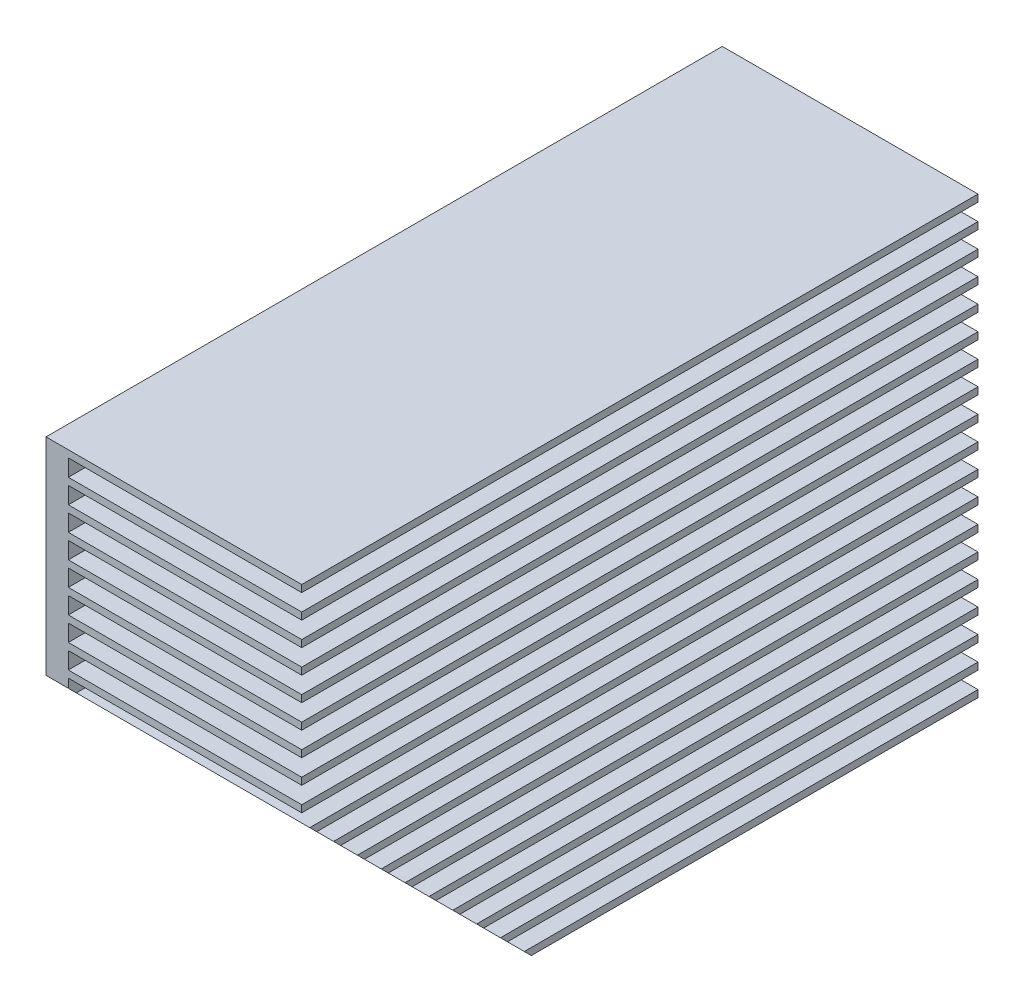
SolidWorks part; units mm, degrees
ref_plane "Front Plane" through (0, 0, 0) normal (0, 0, 1) x (1, 0, 0)
ref_plane "Top Plane" through (0, 0, 0) normal (0, 1, 0) x (1, 0, 0)
ref_plane "Right Plane" through (0, 0, 0) normal (1, 0, 0) x (0, 0, -1)
ref_axis "Axis1" through (0, -55, 0) along (0, 1, 0)
sketch "Sketch1" plane through (0, 0, 0) normal (1, 0, 0) x (0, 0, -1)
  line L1 (48.0658, 31) -> (-48.0658, 31)
  line L2 (48.0658, 31) -> (48.0658, -31)
  line L3 (48.0658, -31) -> (-48.0658, -31)
  line L4 (-48.0658, 31) -> (-48.0658, -31)
  line L5 (48.0658, 31) -> (-48.0658, -31) construction
  line L6 (48.0658, -31) -> (-48.0658, 31) construction
  point P0 (0, 0)
  dimension "D1" = 96.1315
  dimension "D2" = 62
extrude "Boss-Extrude1" add sketch "Sketch1" along normal blind 3.175
sketch "Sketch2" plane through (3.175, 0, 0) normal (1, 0, 0) x (0, 0, -1)
  line L0 (-48.0658, 31) -> (48.0658, 31)
extrude "Extrude-Thin1" add sketch "Sketch2" along normal blind 33.175 thin thin type one direction wall 1
pattern_linear "LPattern1" count 19 spacing 3.3889 along (0, -1, 0) of "Extrude-Thin1"
sketch "Sketch3" plane through (3.175, 0, 0) normal (1, 0, 0) x (0, 0, -1)
  line L0 (-0.0965, -46.3318) -> (-55.4837, 9.0553) construction
  line L1 (-0.0965, -46.3318) -> (-55.4837, 9.0553)
  line L2 (-55.4837, 9.0553) -> (-88.0968, -23.5578)
  line L3 (-88.0968, -23.5578) -> (-32.7097, -78.945)
  line L4 (-32.7097, -78.945) -> (-0.0965, -46.3318)
extrude "Cut-Extrude1" cut sketch "Sketch3" against normal through all both and the other way through all
